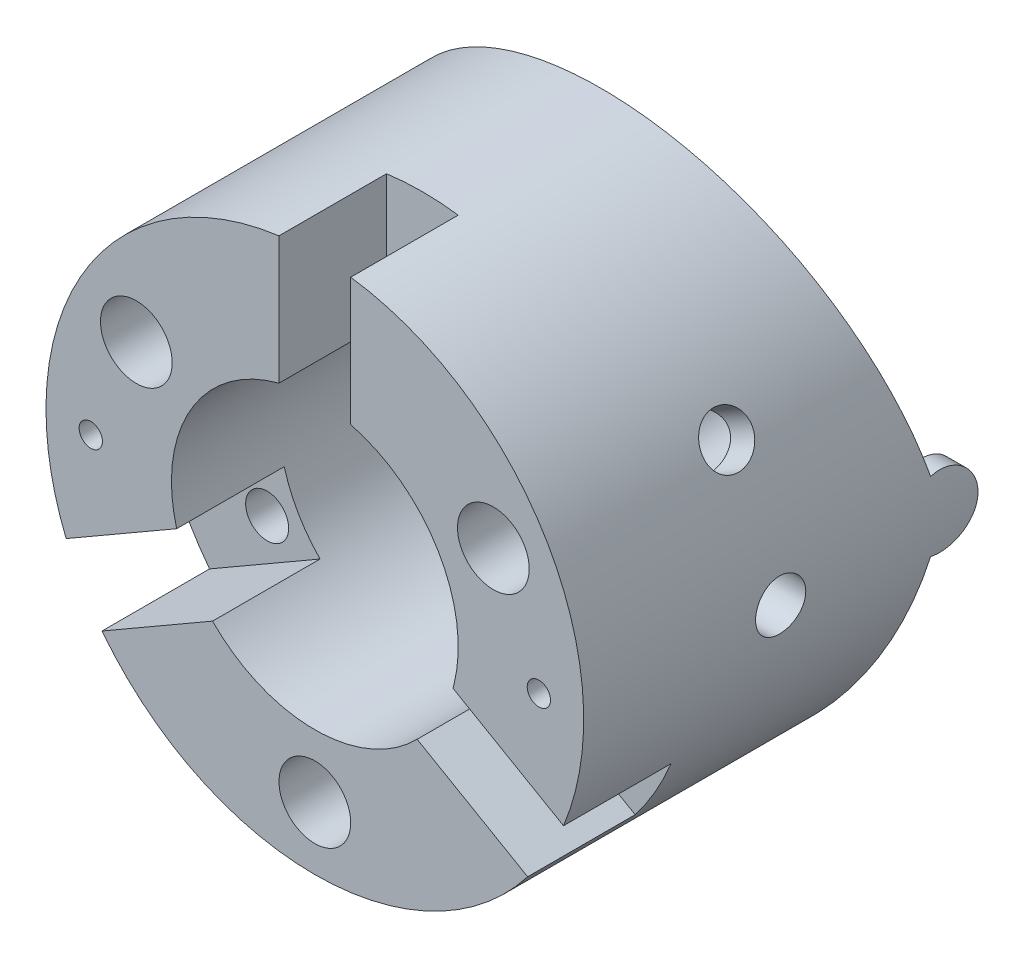
SolidWorks part; units mm, degrees
ref_plane "前视基准面" through (0, 0, 0) normal (0, 0, 1) x (1, 0, 0)
ref_plane "上视基准面" through (0, 0, 0) normal (0, 1, 0) x (1, 0, 0)
ref_plane "右视基准面" through (0, 0, 0) normal (1, 0, 0) x (0, 0, -1)
sketch "草图1" plane through (0, 0, 0) normal (0, 0, 1) x (1, 0, 0)
  circle A0 centre (0, 0) radius 7.5
  dimension "D1" = 15
extrude "凸台-拉伸1" add sketch "草图1" along normal blind 10
sketch "草图2" plane through (0, 0, 10) normal (0, 0, 1) x (1, 0, 0)
  line L0 (0, 0) -> (0, 5) construction
  circle A0 centre (0, 0) radius 5 construction
  circle A1 centre (0, 5) radius 0.6
  circle A2 centre (4.3301, -2.5) radius 0.6
  circle A3 centre (-4.3301, -2.5) radius 0.6
  point P12 (0, 0)
  dimension "D1" = 10
  dimension "D2" = 1.2
  dimension "D3" = 3
extrude "切除-拉伸1" cut sketch "草图2" against normal through all
sketch "草图3" plane through (0, 0, 0) normal (1, 0, 0) x (0, 0, -1)
  line L0 (0, 0) -> (-2.0096, 7.5)
  line L1 (0, 7.5) -> (-10, 7.5) construction
  line L2 (-2.0096, 7.5) -> (0, 7.5)
  line L3 (0, 7.5) -> (0, 0)
  line L4 (0, 0) -> (-2.0096, -7.5)
  line L5 (-10, -7.5) -> (0, -7.5) construction
  line L6 (-2.0096, -7.5) -> (0, -7.5)
  line L7 (0, -7.5) -> (0, 0)
  dimension "D1" = 15
  dimension "D2" = 15
extrude "切除-拉伸2" cut sketch "草图3" against normal through all and the other way through all contours L3 L2 L0 | L6 L7 L4 region at (0, 5, 0.6699) region at (0, -5, 0.6699)
sketch "草图4" plane through (0, 0, 0) normal (1, 0, 0) x (0, 0, -1)
  circle A0 centre (0, 0) radius 1
  dimension "D1" = 2
extrude "凸台-拉伸2" add sketch "草图4" along normal up to surface and the other way up to surface up to face at (7.5, 0, 10) other way up to face at (7.5, 0, 10)
sketch "草图5" plane through (0, 0, 10) normal (0, 0, 1) x (1, 0, 0)
  circle A0 centre (0, 0) radius 4
  dimension "D1" = 8
extrude "切除-拉伸3" cut sketch "草图5" against normal through all
ref_plane "基准面1" through (0, 0, -1) normal (0, 0, -1) x (-1, 0, 0)
sketch "草图6" plane through (0, 0, -1) normal (0, 0, -1) x (-1, 0, 0)
  line L0 (-5.653, 1) -> (-5.653, -1) construction
  line L1 (-3.873, 1) -> (-7.433, 1) construction
  line L2 (-7.433, -1) -> (-3.873, -1) construction
  line L3 (5.653, 1) -> (5.653, -1) construction
  line L4 (7.433, 1) -> (3.873, 1) construction
  line L5 (3.873, -1) -> (7.433, -1) construction
  line L6 (0, 0) -> (0, 8.2847) construction
  line L7 (-6.903, 1) -> (-4.403, 1)
  line L8 (-6.903, 1) -> (-6.903, -1)
  line L9 (-6.903, -1) -> (-4.403, -1)
  line L10 (-4.403, 1) -> (-4.403, -1)
  line L11 (-6.903, 1) -> (-4.403, -1) construction
  line L12 (-6.903, -1) -> (-4.403, 1) construction
  line L13 (6.903, 1) -> (6.903, -1)
  line L14 (6.903, -1) -> (4.403, -1)
  line L15 (4.403, 1) -> (4.403, -1)
  line L16 (6.903, 1) -> (4.403, 1)
  point P12 (-5.653, 0)
  dimension "D1" = 2.5
extrude "切除-拉伸4" cut sketch "草图6" against normal blind 1
sketch "草图7" plane through (0, 0, 10) normal (0, 0, 1) x (1, 0, 0)
  line L0 (0, 0) -> (6.25, 0) construction
  line L1 (6.25, 0) -> (-6.25, 0) construction
  circle A0 centre (0, 0) radius 6.25 construction
  circle A3 centre (-6.25, 0) radius 0.325
  circle A4 centre (6.25, 0) radius 0.325
  dimension "D1" = 12.5
  dimension "D2" = 0.65
  dimension "D3" = 0.65
extrude "切除-拉伸5" cut sketch "草图7" against normal through all
sketch "草图8" plane through (0, 0, 10) normal (0, 0, 1) x (1, 0, 0)
  line L0 (0, 7.5) -> (0, 0) construction
  line L1 (7.5592, -3.2096) -> (6.5592, -4.9416)
  line L2 (-1, 8.1512) -> (1, 8.1512)
  line L3 (-1, 8.1512) -> (-1, 3.1512)
  line L4 (-1, 3.1512) -> (1, 3.1512)
  line L5 (1, 8.1512) -> (1, 3.1512)
  line L6 (-1, 8.1512) -> (1, 3.1512) construction
  line L7 (-1, 3.1512) -> (1, 8.1512) construction
  line L8 (7.5592, -3.2096) -> (3.229, -0.7096)
  line L9 (3.229, -0.7096) -> (2.229, -2.4416)
  line L10 (6.5592, -4.9416) -> (2.229, -2.4416)
  line L11 (-6.5592, -4.9416) -> (-7.5592, -3.2096)
  line L12 (-6.5592, -4.9416) -> (-2.229, -2.4416)
  line L13 (-2.229, -2.4416) -> (-3.229, -0.7096)
  line L14 (-7.5592, -3.2096) -> (-3.229, -0.7096)
  circle A0 centre (0, 0) radius 7.5 construction
  point P5 (0, 5.6512)
  point P21 (0, 0)
  dimension "D1" = 2
  dimension "D2" = 5
  dimension "D3" = 3
extrude "切除-拉伸6" cut sketch "草图8" against normal blind 3
sketch "草图9" plane through (0, 0, 0) normal (1, 0, 0) x (0, 0, -1)
  line L0 (-4.5048, 7.5) -> (-4.5048, -7.5) construction
  line L1 (-2.0096, 7.5) -> (-7, 7.5) construction
  line L2 (-10, -7.5) -> (-2.0096, -7.5) construction
  line L3 (0, 0) -> (-10, 0) construction
  line L4 (-10, 7.433) -> (-10, -2.8505) construction
  circle A0 centre (-4.5048, 0) radius 0.7
  dimension "D1" = 1.4
extrude "切除-拉伸7" cut sketch "草图9" against normal blind 1.5 from surface contours A0 starting at face at (0, 0, 1.0048)
sketch "草图10" plane through (0, 0, 10) normal (0, 0, 1) x (1, 0, 0)
  line L0 (0, 0) -> (0, -5.75) construction
  circle A0 centre (0, 0) radius 5.75 construction
  circle A1 centre (0, -5.75) radius 1
  circle A2 centre (-4.9796, 2.875) radius 1
  circle A3 centre (4.9796, 2.875) radius 1
  point P12 (0, 0)
  dimension "D1" = 11.5
  dimension "D2" = 2
  dimension "D3" = 3
extrude "切除-拉伸8" cut sketch "草图10" against normal through all
ref_plane "基准面2" through (-7.5, 0, 0) normal (-1, 0, 0) x (0, 0, 1)
sketch "草图12" plane through (-7.5, 0, 0) normal (-1, 0, 0) x (0, 0, 1)
  spline S0 degree 3 poles (5.2048, 0) (5.2048, 0.0512) (5.1991, 0.1027) (5.188, 0.1527) (5.1708, 0.2293) (5.1402, 0.3039) (5.0987, 0.3705) (5.0573, 0.4369) (5.0038, 0.4971) (4.9428, 0.5461) (4.8819, 0.5949) (4.8119, 0.6339) (4.7383, 0.6599) (4.6647, 0.6859) (4.5856, 0.6997) (4.5076, 0.7) (4.4292, 0.7003) (4.3497, 0.6871) (4.2756, 0.6614) (4.2015, 0.6357) (4.1308, 0.5969) (4.0694, 0.5481) (4.0082, 0.4995) (3.9545, 0.4396) (3.9128, 0.3735) (3.8712, 0.3076) (3.8403, 0.2336) (3.8228, 0.1576) (3.8052, 0.0814) (3.8005, 0.0012) (3.809, -0.0765) (3.8176, -0.1545) (3.8398, -0.2321) (3.8737, -0.3028) (3.9076, -0.3734) (3.9541, -0.4392) (4.0095, -0.4947) (4.0647, -0.5499) (4.1301, -0.5964) (4.2004, -0.6304) (4.2707, -0.6643) (4.3477, -0.6866) (4.4252, -0.6955) (4.503, -0.7044) (4.5834, -0.7) (4.6597, -0.6827) (4.7362, -0.6653) (4.8108, -0.6344) (4.8772, -0.5927) (4.9435, -0.5511) (5.0035, -0.4974) (5.0523, -0.4362) (5.1009, -0.3751) (5.1398, -0.3049) (5.1655, -0.2311) (5.1913, -0.1574) (5.2048, -0.0782) (5.2048, 0) (5.2048, 0.0512) (5.1991, 0.1027) knots -0.053546 0 0 0 0.03479 0.03479 0.03479 0.088576 0.088576 0.088576 0.142263 0.142263 0.142263 0.195743 0.195743 0.195743 0.249231 0.249231 0.249231 0.302931 0.302931 0.302931 0.356714 0.356714 0.356714 0.410324 0.410324 0.410324 0.463776 0.463776 0.463776 0.517327 0.517327 0.517327 0.571084 0.571084 0.571084 0.624831 0.624831 0.624831 0.678367 0.678367 0.678367 0.73182 0.73182 0.73182 0.785447 0.785447 0.785447 0.839235 0.839235 0.839235 0.892918 0.892918 0.892918 0.946454 0.946454 0.946454 1 1 1 1.03479 1.03479 1.03479 only from (5.2048, 0) to (5.2048, 0) construction
  spline S1 degree 3 poles (5.2048, 0) (5.2048, 0.0512) (5.1991, 0.1027) (5.188, 0.1527) (5.1708, 0.2293) (5.1402, 0.3039) (5.0987, 0.3705) (5.0573, 0.4369) (5.0038, 0.4971) (4.9428, 0.5461) (4.8819, 0.5949) (4.8119, 0.6339) (4.7383, 0.6599) (4.6647, 0.6859) (4.5856, 0.6997) (4.5076, 0.7) (4.4292, 0.7003) (4.3497, 0.6871) (4.2756, 0.6614) (4.2015, 0.6357) (4.1308, 0.5969) (4.0694, 0.5481) (4.0082, 0.4995) (3.9545, 0.4396) (3.9128, 0.3735) (3.8712, 0.3076) (3.8403, 0.2336) (3.8228, 0.1576) (3.8052, 0.0814) (3.8005, 0.0012) (3.809, -0.0765) (3.8176, -0.1545) (3.8398, -0.2321) (3.8737, -0.3028) (3.9076, -0.3734) (3.9541, -0.4392) (4.0095, -0.4947) (4.0647, -0.5499) (4.1301, -0.5964) (4.2004, -0.6304) (4.2707, -0.6643) (4.3477, -0.6866) (4.4252, -0.6955) (4.503, -0.7044) (4.5834, -0.7) (4.6597, -0.6827) (4.7362, -0.6653) (4.8108, -0.6344) (4.8772, -0.5927) (4.9435, -0.5511) (5.0035, -0.4974) (5.0523, -0.4362) (5.1009, -0.3751) (5.1398, -0.3049) (5.1655, -0.2311) (5.1913, -0.1574) (5.2048, -0.0782) (5.2048, 0) (5.2048, 0.0512) (5.1991, 0.1027) knots -0.053546 0 0 0 0.03479 0.03479 0.03479 0.088576 0.088576 0.088576 0.142263 0.142263 0.142263 0.195743 0.195743 0.195743 0.249231 0.249231 0.249231 0.302931 0.302931 0.302931 0.356714 0.356714 0.356714 0.410324 0.410324 0.410324 0.463776 0.463776 0.463776 0.517327 0.517327 0.517327 0.571084 0.571084 0.571084 0.624831 0.624831 0.624831 0.678367 0.678367 0.678367 0.73182 0.73182 0.73182 0.785447 0.785447 0.785447 0.839235 0.839235 0.839235 0.892918 0.892918 0.892918 0.946454 0.946454 0.946454 1 1 1 1.03479 1.03479 1.03479 only from (5.2048, 0) to (5.2048, 0)
extrude "切除-拉伸9" cut sketch "草图12" against normal blind 1.25
ref_plane "基准面3" through (-6.4952, 3.75, 0) normal (-0.866, 0.5, 0) x (0, 0, -1)
sketch "草图13" plane through (-6.4952, 3.75, 0) normal (-0.866, 0.5, 0) x (0, 0, -1)
  line L0 (-10, 1) -> (-10, -1) construction
  line L1 (-10, 1) -> (-10, -1)
  line L2 (-10, 0) -> (0, 0) construction
  circle A0 centre (-5, 0) radius 0.7
  dimension "D1" = 1.4
extrude "切除-拉伸10" cut sketch "草图13" against normal blind 1.5 contours A0
pattern_circular "阵列(圆周)1" count 3 over 360 about axis through (0, 0, 10) along (0, 0, 1) of "切除-拉伸10"
